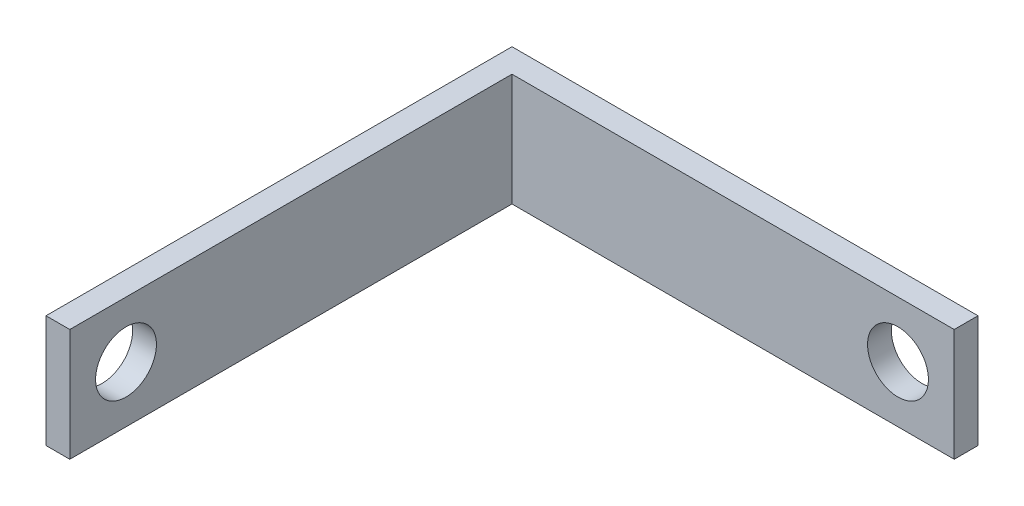
SolidWorks part; units mm, degrees
ref_plane "Front Plane" through (0, 0, 0) normal (0, 0, 1) x (1, 0, 0)
ref_plane "Top Plane" through (0, 0, 0) normal (0, 1, 0) x (1, 0, 0)
ref_plane "Right Plane" through (0, 0, 0) normal (1, 0, 0) x (0, 0, -1)
sketch "Sketch1" plane through (0, 0, 0) normal (0, 1, 0) x (1, 0, 0)
  line L0 (-26.5437, 0) -> (0, 0) construction
  line L1 (-3.75, 25.75) -> (3.75, 25.75)
  line L2 (-3.75, 25.75) -> (-3.75, 27.3375) construction
  line L3 (-3.75, 27.3375) -> (3.75, 27.3375)
  line L4 (3.75, 25.75) -> (3.75, 27.3375)
  line L5 (-3.75, 25.75) -> (3.75, 27.3375) construction
  line L6 (-3.75, 27.3375) -> (3.75, 25.75) construction
  line L7 (-27.3375, 3.75) -> (-25.75, 3.75) construction
  line L8 (-27.3375, 3.75) -> (-27.3375, -3.75)
  line L9 (-27.3375, -3.75) -> (-25.75, -3.75)
  line L10 (-25.75, 3.75) -> (-25.75, -3.75)
  line L11 (-27.3375, 3.75) -> (-25.75, -3.75) construction
  line L12 (-27.3375, -3.75) -> (-25.75, 3.75) construction
  line L13 (0, 0) -> (0, 26.5437) construction
  line L14 (-25.75, 3.75) -> (-25.75, 25.75)
  line L15 (-25.75, 25.75) -> (-3.75, 25.75)
  line L16 (-3.75, 27.3375) -> (-27.3375, 27.3375)
  line L17 (-27.3375, 27.3375) -> (-27.3375, 3.75)
  arc A0 (-25.75, 3.75) -> (-3.75, 25.75) centre (-3.75, 3.75) cw construction
  arc A1 (-27.3375, 3.75) -> (-3.75, 27.3375) centre (-3.75, 3.75) cw construction
  point P0 (0, 26.5437)
  point P5 (-26.5437, 0)
  dimension "D3" = 22
  dimension "D1" = 1.5875
  dimension "D2" = 7.5
extrude "Boss-Extrude1" add sketch "Sketch1" along normal mid plane 7.5 contours L10 L7 L8 L9 | L1 L4 L3 L2 region at (-14.75, 0, -26.1896)
sketch "Sketch2" plane through (-25.75, 0, 0) normal (1, 0, 0) x (0, 0, -1)
  circle A0 centre (0, 0) radius 2.03
  dimension "D1" = 4.06
extrude "Cut-Extrude1" cut sketch "Sketch2" against normal through all
sketch "Sketch3" plane through (0, 0, -25.75) normal (0, 0, 1) x (1, 0, 0)
  circle A0 centre (0, 0) radius 2.03
  dimension "D1" = 4.06
extrude "Cut-Extrude2" cut sketch "Sketch3" against normal through all
